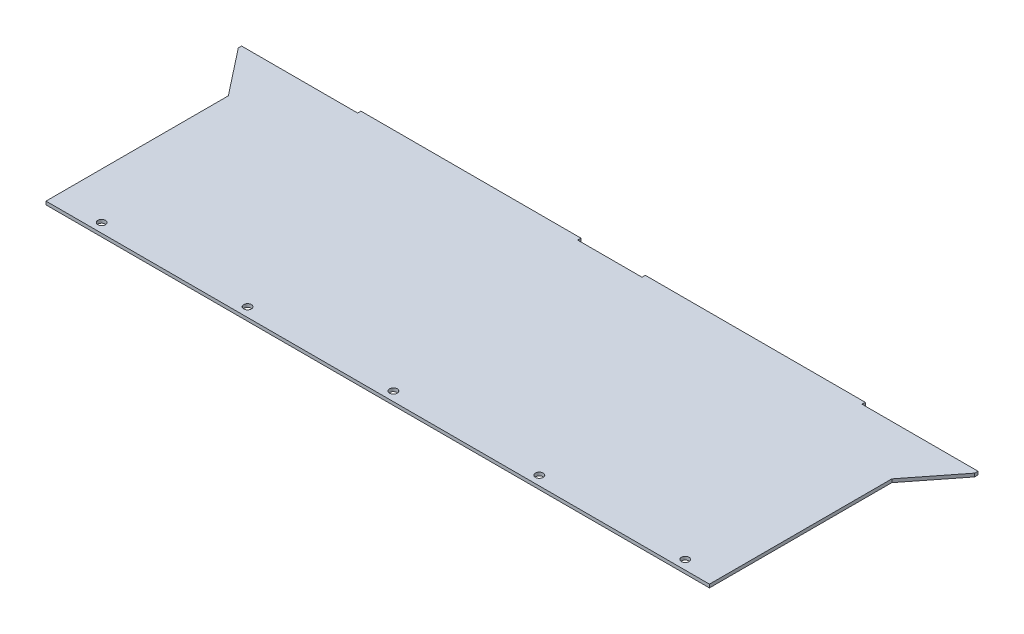
SolidWorks part; units mm, degrees
material "6061-T6 (SS)"
ref_plane "X-Y Datum" through (0, 0, 0) normal (0, 0, 1) x (1, 0, 0)
ref_plane "X-Z Datum" through (0, 0, 0) normal (0, 1, 0) x (1, 0, 0)
ref_plane "Y-Z Datum" through (0, 0, 0) normal (1, 0, 0) x (0, 0, -1)
sketch "Sketch1" plane through (0, 0, 0) normal (0, 1, 0) x (1, 0, 0)
  line L1 (-317.6778, 111.125) -> (317.6778, 111.125)
  line L2 (-317.6778, 111.125) -> (-317.6778, -111.125)
  line L3 (-317.6778, -111.125) -> (317.6778, -111.125)
  line L4 (317.6778, 111.125) -> (317.6778, -111.125)
  line L5 (-317.6778, 111.125) -> (317.6778, -111.125) construction
  line L6 (-317.6778, -111.125) -> (317.6778, 111.125) construction
  point P0 (0, 0)
  dimension "D1" = 635.3556
  dimension "D2" = 222.25
extrude "Boss-Extrude1" add sketch "Sketch1" along normal mid plane 3.175
sketch "Sketch2" plane through (0, 0, -111.125) normal (0, 0, -1) x (-1, 0, 0)
  line L0 (-241.4778, -1.5875) -> (-241.4778, 1.5875) construction
  line L1 (241.4778, -1.5875) -> (241.4778, 1.5875)
  line L2 (-241.4778, -1.5875) -> (-241.4778, 1.5875)
  line L3 (-241.4778, -1.5875) -> (-241.4778, 1.5875)
  line L4 (241.4778, -1.5875) -> (241.4778, 1.5875) construction
  line L5 (241.4778, -1.5875) -> (241.4778, 1.5875)
  line L20 (-317.6778, -1.5875) -> (317.6778, -1.5875) construction
  line L21 (-241.4778, -1.5875) -> (-30.8229, -1.5875)
  line L22 (30.8229, -1.5875) -> (241.4778, -1.5875)
  line L40 (30.8229, -1.5875) -> (30.8229, 1.5875)
  line L41 (30.8229, 1.5875) -> (241.4778, 1.5875)
  line L57 (-241.4778, 1.5875) -> (-30.8229, 1.5875)
  line L58 (-30.8229, 1.5875) -> (-30.8229, -1.5875)
  line M22 (-317.6778, -1.5875) -> (317.6778, -1.5875)
  line M24 (317.6778, 1.5875) -> (-317.6778, 1.5875)
extrude "Boss-Extrude2" add sketch "Sketch2" along normal blind 3.175 contours L58 L2 M24 M22 | L40 L1 M22 M24 region at (-136.1504, 0, -111.125) region at (136.1504, 0, -111.125)
sketch "Sketch3" plane through (0, 1.5875, 0) normal (0, 1, 0) x (1, 0, 0)
  line L0 (-317.6778, 111.125) -> (-352.6028, 111.125)
  line L1 (-352.6028, 111.125) -> (-352.6028, 107.95)
  line L2 (-352.6028, 107.95) -> (-317.6778, 63.5)
  line L3 (-317.6778, 111.125) -> (-317.6778, -111.125) construction
  line L16 (317.6778, -111.125) -> (317.6778, 111.125)
  line L17 (317.6778, 111.125) -> (241.4778, 111.125)
  line L18 (241.4778, 111.125) -> (241.4778, 114.3)
  line L19 (30.8229, 114.3) -> (30.8229, 111.125)
  line L20 (30.8229, 111.125) -> (-30.8229, 111.125)
  line L21 (-30.8229, 111.125) -> (-30.8229, 114.3)
  line L22 (-241.4778, 114.3) -> (-241.4778, 111.125)
  line L23 (-241.4778, 111.125) -> (-317.6778, 111.125)
  line L24 (241.4778, 114.3) -> (30.8229, 114.3)
  line L25 (241.4778, 114.3) -> (30.8229, 114.3)
  line L26 (-317.6778, 111.125) -> (-317.6778, -111.125)
  line L27 (-317.6778, -111.125) -> (317.6778, -111.125)
  line L38 (-317.6778, 111.125) -> (-317.6778, 63.5)
  line L40 (-30.8229, 114.3) -> (-241.4778, 114.3)
  line L41 (-30.8229, 114.3) -> (-241.4778, 114.3)
  line M26 (-317.6778, 111.125) -> (-317.6778, -111.125)
  dimension "D1" = 34.925
  dimension "D2" = 3.175
  dimension "D3" = 44.45
  dimension "D4" = 0
extrude "Boss-Extrude3" add sketch "Sketch3" against normal blind 3.175 contours L1 L2 L0 M26 region at (-330.0471, 1.5875, -95.1839)
mirror "Mirror1" about plane through (0, 0, 0) normal (1, 0, 0) of "Boss-Extrude3"
sketch "Sketch4" plane through (0, 1.5875, 0) normal (0, 1, 0) x (1, 0, 0)
  line L0 (-273.2278, -111.125) -> (-273.2278, -102.235)
  line L1 (-317.6778, -111.125) -> (317.6778, -111.125) construction
  line L2 (-273.2278, -102.235) -> (-317.6778, -102.235)
  line L3 (-317.6778, 63.5) -> (-317.6778, -111.125) construction
  circle A0 centre (-273.2278, -102.235) radius 3.675
extrude "Cut-Extrude1" cut sketch "Sketch4" against normal blind 10 contours L0 A0 L2 | L2 A0 L0 region at (-274.7875, 1.5875, 103.7947) region at (-272.7079, 1.5875, 101.7151)
pattern_linear "LPattern1" count 5 spacing 139.7 along (1, 0, 0) of "Cut-Extrude1"
